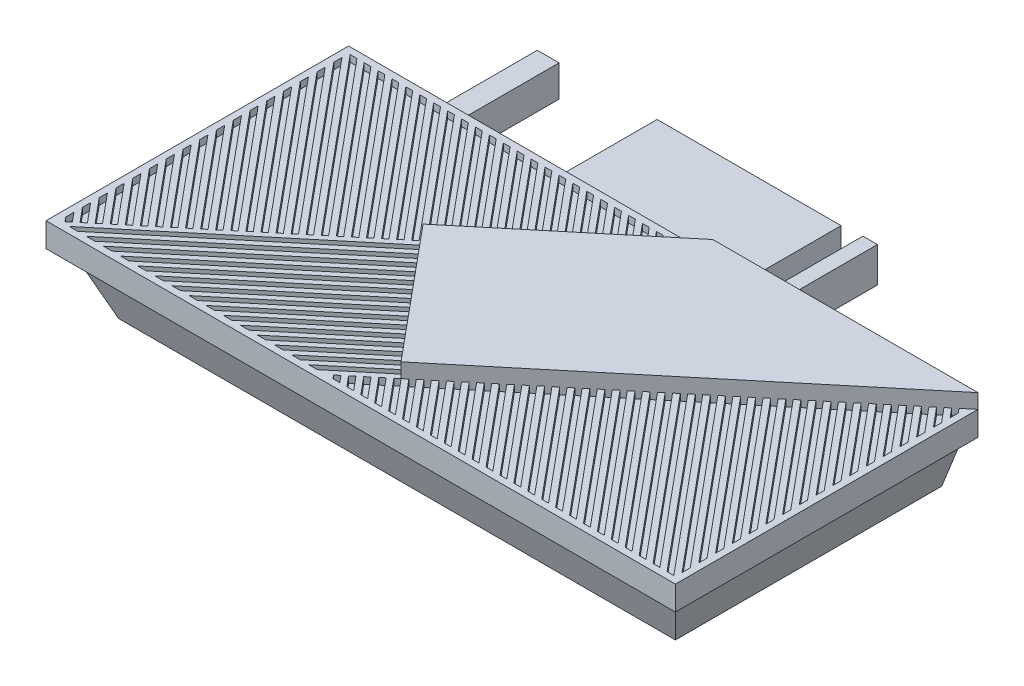
SolidWorks part; units mm, degrees
ref_plane "Front Plane" through (0, 0, 0) normal (0, 0, 1) x (1, 0, 0)
ref_plane "Top Plane" through (0, 0, 0) normal (0, 1, 0) x (1, 0, 0)
ref_plane "Right Plane" through (0, 0, 0) normal (1, 0, 0) x (0, 0, -1)
sketch "Sketch1" plane through (0, 0, 0) normal (0, 1, 0) x (1, 0, 0)
  line L1 (-130, 62.5) -> (130, 62.5)
  line L2 (-130, 62.5) -> (-130, -62.5)
  line L3 (-130, -62.5) -> (130, -62.5)
  line L4 (130, 62.5) -> (130, -62.5)
  line L5 (-130, 62.5) -> (130, -62.5) construction
  line L6 (-130, -62.5) -> (130, 62.5) construction
  point P0 (0, 0)
  dimension "D1" = 260
  dimension "D2" = 125
extrude "Boss-Extrude1" add sketch "Sketch1" against normal blind 10
ref_plane "Plane1" through (0, -35, 0) normal (0, -1, 0) x (-1, 0, 0)
sketch "Sketch2" plane through (0, -35, 0) normal (0, -1, 0) x (-1, 0, 0)
  line L1 (-115, -47.5) -> (115, -47.5)
  line L2 (-115, -47.5) -> (-115, 62.5)
  line L3 (-115, 62.5) -> (115, 62.5)
  line L4 (115, -47.5) -> (115, 62.5)
  line L5 (-130, 62.5) -> (130, 62.5) construction
  point P6 (0, 62.5)
  dimension "D1" = 110
  dimension "D2" = 230
sketch "Sketch3" plane through (0, -10, 0) normal (0, -1, 0) x (1, 0, 0)
  line L0 (130, -62.5) -> (-130, -62.5) construction
  line L1 (-125, 57.5) -> (125, 57.5)
  line L2 (-125, 57.5) -> (-125, -62.5)
  line L3 (-125, -62.5) -> (125, -62.5)
  line L4 (125, 57.5) -> (125, -62.5)
  point P10 (0, 57.5)
  dimension "D1" = 250
  dimension "D2" = 120
loft "Loft1" add profiles "Sketch2", "Sketch3" connector at (115, -35, 47.5) connector at (125, -10, 57.5)
sketch "Sketch4" plane through (0, 0, 0) normal (0, 1, 0) x (1, 0, 0)
  line L0 (130, 62.5) -> (-0.1894, -45.6603)
  line L1 (-0.1894, -45.6603) -> (-44.9215, 8.1825)
  line L2 (-44.9215, 8.1825) -> (20.4589, 62.5)
  line L3 (130, 62.5) -> (-130, 62.5) construction
  line L4 (20.4589, 62.5) -> (130, 62.5)
  line L6 (-44.9215, 8.1825) -> (-130, -62.5) construction
  dimension "D1" = 70
  dimension "D3" = 85
extrude "Boss-Extrude2" add sketch "Sketch4" along normal blind 6
shell "Shell2" thickness 2.75 removed face at (-3.5217, 0, -3.5746)
sketch "Sketch7" plane through (0, 0, 0) normal (0, 1, 0) x (1, 0, 0)
  line L0 (-0.1894, -45.6603) -> (-44.9215, 8.1825)
  line L2 (-44.9215, 8.1825) -> (20.4589, 62.5)
  line L3 (20.4589, 62.5) -> (130, 62.5)
  line L4 (130, 62.5) -> (-0.1894, -45.6603)
extrude "Boss-Extrude5" add sketch "Sketch7" against normal blind 2.75
sketch "Sketch6" plane through (0, 0, 0) normal (0, 1, 0) x (1, 0, 0)
  line L0 (-44.9215, 8.1825) -> (-130, -62.5)
  line L1 (-130, -62.5) -> (-126.4664, -62.5)
  line L2 (-130, -62.5) -> (130, -62.5) construction
  line L3 (-126.4664, -62.5) -> (-43.4786, 6.4456)
  line L4 (-44.9215, 8.1825) -> (-0.1894, -45.6603) construction
  line L5 (-43.4786, 6.4456) -> (-44.9215, 8.1825)
  line L6 (-123.5805, -65.9737) -> (-40.5926, 2.9719)
  line L7 (-42.0356, 4.7087) -> (-127.1141, -65.9737)
  line L8 (-127.1141, -65.9737) -> (-123.5805, -65.9737)
  line L9 (-40.5926, 2.9719) -> (-42.0356, 4.7087)
  line L10 (-120.6945, -69.4475) -> (-37.7067, -0.5018)
  line L11 (-39.1496, 1.235) -> (-124.2281, -69.4475)
  line L12 (-124.2281, -69.4475) -> (-120.6945, -69.4475)
  line L13 (-37.7067, -0.5018) -> (-39.1496, 1.235)
  line L14 (-117.8086, -72.9212) -> (-34.8207, -3.9756)
  line L15 (-36.2637, -2.2387) -> (-121.3422, -72.9212)
  line L16 (-121.3422, -72.9212) -> (-117.8086, -72.9212)
  line L17 (-34.8207, -3.9756) -> (-36.2637, -2.2387)
  line L18 (-114.9227, -76.3949) -> (-31.9348, -7.4493)
  line L19 (-33.3778, -5.7124) -> (-118.4562, -76.3949)
  line L20 (-118.4562, -76.3949) -> (-114.9227, -76.3949)
  line L21 (-31.9348, -7.4493) -> (-33.3778, -5.7124)
  line L22 (-112.0367, -79.8686) -> (-29.0489, -10.923)
  line L23 (-30.4918, -9.1862) -> (-115.5703, -79.8686)
  line L24 (-115.5703, -79.8686) -> (-112.0367, -79.8686)
  line L25 (-29.0489, -10.923) -> (-30.4918, -9.1862)
  line L26 (-109.1508, -83.3424) -> (-26.1629, -14.3967)
  line L27 (-27.6059, -12.6599) -> (-112.6844, -83.3424)
  line L28 (-112.6844, -83.3424) -> (-109.1508, -83.3424)
  line L29 (-26.1629, -14.3967) -> (-27.6059, -12.6599)
  line L30 (-106.2648, -86.8161) -> (-23.277, -17.8705)
  line L31 (-24.7199, -16.1336) -> (-109.7984, -86.8161)
  line L32 (-109.7984, -86.8161) -> (-106.2648, -86.8161)
  line L33 (-23.277, -17.8705) -> (-24.7199, -16.1336)
  line L34 (-103.3789, -90.2898) -> (-20.391, -21.3442)
  line L35 (-21.834, -19.6073) -> (-106.9125, -90.2898)
  line L36 (-106.9125, -90.2898) -> (-103.3789, -90.2898)
  line L37 (-20.391, -21.3442) -> (-21.834, -19.6073)
  line L38 (-100.4929, -93.7635) -> (-17.5051, -24.8179)
  line L39 (-18.9481, -23.0811) -> (-104.0265, -93.7635)
  line L40 (-104.0265, -93.7635) -> (-100.4929, -93.7635)
  line L41 (-17.5051, -24.8179) -> (-18.9481, -23.0811)
  line L42 (-97.607, -97.2373) -> (-14.6191, -28.2916)
  line L43 (-16.0621, -26.5548) -> (-101.1406, -97.2373)
  line L44 (-101.1406, -97.2373) -> (-97.607, -97.2373)
  line L45 (-14.6191, -28.2916) -> (-16.0621, -26.5548)
  line L46 (-94.7211, -100.711) -> (-11.7332, -31.7654)
  line L47 (-13.1762, -30.0285) -> (-98.2546, -100.711)
  line L48 (-98.2546, -100.711) -> (-94.7211, -100.711)
  line L49 (-11.7332, -31.7654) -> (-13.1762, -30.0285)
  line L50 (-91.8351, -104.1847) -> (-8.8473, -35.2391)
  line L51 (-10.2902, -33.5022) -> (-95.3687, -104.1847)
  line L52 (-95.3687, -104.1847) -> (-91.8351, -104.1847)
  line L53 (-8.8473, -35.2391) -> (-10.2902, -33.5022)
  line L54 (-88.9492, -107.6584) -> (-5.9613, -38.7128)
  line L55 (-7.4043, -36.976) -> (-92.4828, -107.6584)
  line L56 (-92.4828, -107.6584) -> (-88.9492, -107.6584)
  line L57 (-5.9613, -38.7128) -> (-7.4043, -36.976)
  line L58 (-86.0632, -111.1322) -> (-3.0754, -42.1865)
  line L59 (-4.5184, -40.4497) -> (-89.5968, -111.1322)
  line L60 (-89.5968, -111.1322) -> (-86.0632, -111.1322)
  line L61 (-3.0754, -42.1865) -> (-4.5184, -40.4497)
  line L62 (-83.1773, -114.6059) -> (-0.1894, -45.6603)
  line L63 (-1.6324, -43.9234) -> (-86.7109, -114.6059)
  line L64 (-86.7109, -114.6059) -> (-83.1773, -114.6059)
  line L65 (-0.1894, -45.6603) -> (-1.6324, -43.9234)
  dimension "D1" = 2.2581
  dimension "D3" = 70
  dimension "D2" = 16
extrude "Boss-Extrude6" add sketch "Sketch6" against normal blind 2.75
sketch "Sketch8" plane through (0, -10, 0) normal (0, -1, 0) x (1, 0, 0)
  line L1 (-130, 62.5) -> (15.5362, 62.5)
  line L2 (-130, 62.5) -> (-130, 143.892)
  line L3 (-130, 143.892) -> (15.5362, 143.892)
  line L4 (15.5362, 62.5) -> (15.5362, 143.892)
extrude "Cut-Extrude1" cut sketch "Sketch8" against normal through all both and the other way through all
sketch "Sketch9" plane through (0, 0, -62.5) normal (0, 0, -1) x (-1, 0, 0)
  line L0 (130, -10) -> (130, 0) construction
  line L1 (-20.4589, 0) -> (130, 0) construction
  circle A0 centre (111.5, -14.125) radius 6.625
  circle A1 centre (60, -14.125) radius 6.625
  dimension "D3" = 13.25
  dimension "D1" = 18.5
  dimension "D2" = 14.125
  dimension "D4" = 70
extrude "Boss-Extrude7" add sketch "Sketch9" along normal blind 3.3
sketch "Sketch10" plane through (0, 0, -65.8) normal (0, 0, -1) x (-1, 0, 0)
  circle A0 centre (60, -14.125) radius 5
  circle A1 centre (111.5, -14.125) radius 5
  dimension "D1" = 10
extrude "Cut-Extrude4" cut sketch "Sketch10" against normal blind 1
mirror "Mirror1" about plane through (0, 0, 0) normal (1, 0, 0) of "Cut-Extrude4", "Boss-Extrude7"
sketch "Sketch11" plane through (0, 0, 0) normal (0, 1, 0) x (1, 0, 0)
  line L0 (17.1488, 59.75) -> (15.412, 58.307)
  line L1 (20.4589, 62.5) -> (-44.9215, 8.1825) construction
  line L2 (15.412, 58.307) -> (-80.4425, 173.6843)
  line L3 (-80.4425, 173.6843) -> (-78.7056, 175.1273)
  line L4 (-78.7056, 175.1273) -> (17.1488, 59.75)
  line L5 (12.0103, 55.481) -> (-83.8441, 170.8583)
  line L6 (-82.1073, 172.3012) -> (13.7472, 56.9239)
  line L7 (13.7472, 56.9239) -> (12.0103, 55.481)
  line L8 (-83.8441, 170.8583) -> (-82.1073, 172.3012)
  line L9 (8.6087, 52.6549) -> (-87.2458, 168.0322)
  line L10 (-85.5089, 169.4752) -> (10.3455, 54.0979)
  line L11 (10.3455, 54.0979) -> (8.6087, 52.6549)
  line L12 (-87.2458, 168.0322) -> (-85.5089, 169.4752)
  line L13 (5.207, 49.8288) -> (-90.6474, 165.2061)
  line L14 (-88.9106, 166.6491) -> (6.9439, 51.2718)
  line L15 (6.9439, 51.2718) -> (5.207, 49.8288)
  line L16 (-90.6474, 165.2061) -> (-88.9106, 166.6491)
  line L17 (1.8054, 47.0028) -> (-94.0491, 162.3801)
  line L18 (-92.3122, 163.823) -> (3.5422, 48.4457)
  line L19 (3.5422, 48.4457) -> (1.8054, 47.0028)
  line L20 (-94.0491, 162.3801) -> (-92.3122, 163.823)
  line L21 (-1.5963, 44.1767) -> (-97.4507, 159.554)
  line L22 (-95.7139, 160.997) -> (0.1406, 45.6197)
  line L23 (0.1406, 45.6197) -> (-1.5963, 44.1767)
  line L24 (-97.4507, 159.554) -> (-95.7139, 160.997)
  line L25 (-4.9979, 41.3507) -> (-100.8524, 156.728)
  line L26 (-99.1155, 158.1709) -> (-3.2611, 42.7936)
  line L27 (-3.2611, 42.7936) -> (-4.9979, 41.3507)
  line L28 (-100.8524, 156.728) -> (-99.1155, 158.1709)
  line L29 (-8.3996, 38.5246) -> (-104.254, 153.9019)
  line L30 (-102.5172, 155.3449) -> (-6.6627, 39.9676)
  line L31 (-6.6627, 39.9676) -> (-8.3996, 38.5246)
  line L32 (-104.254, 153.9019) -> (-102.5172, 155.3449)
  line L33 (-11.8012, 35.6985) -> (-107.6557, 151.0758)
  line L34 (-105.9188, 152.5188) -> (-10.0644, 37.1415)
  line L35 (-10.0644, 37.1415) -> (-11.8012, 35.6985)
  line L36 (-107.6557, 151.0758) -> (-105.9188, 152.5188)
  line L37 (-15.2029, 32.8725) -> (-111.0573, 148.2498)
  line L38 (-109.3205, 149.6927) -> (-13.466, 34.3154)
  line L39 (-13.466, 34.3154) -> (-15.2029, 32.8725)
  line L40 (-111.0573, 148.2498) -> (-109.3205, 149.6927)
  line L41 (-18.6045, 30.0464) -> (-114.459, 145.4237)
  line L42 (-112.7221, 146.8667) -> (-16.8677, 31.4894)
  line L43 (-16.8677, 31.4894) -> (-18.6045, 30.0464)
  line L44 (-114.459, 145.4237) -> (-112.7221, 146.8667)
  line L45 (-22.0062, 27.2203) -> (-117.8606, 142.5976)
  line L46 (-116.1238, 144.0406) -> (-20.2693, 28.6633)
  line L47 (-20.2693, 28.6633) -> (-22.0062, 27.2203)
  line L48 (-117.8606, 142.5976) -> (-116.1238, 144.0406)
  line L49 (-25.4078, 24.3943) -> (-121.2623, 139.7716)
  line L50 (-119.5254, 141.2145) -> (-23.671, 25.8372)
  line L51 (-23.671, 25.8372) -> (-25.4078, 24.3943)
  line L52 (-121.2623, 139.7716) -> (-119.5254, 141.2145)
  line L53 (-28.8095, 21.5682) -> (-124.664, 136.9455)
  line L54 (-122.9271, 138.3885) -> (-27.0726, 23.0112)
  line L55 (-27.0726, 23.0112) -> (-28.8095, 21.5682)
  line L56 (-124.664, 136.9455) -> (-122.9271, 138.3885)
  line L57 (-32.2111, 18.7422) -> (-128.0656, 134.1194)
  line L58 (-126.3287, 135.5624) -> (-30.4743, 20.1851)
  line L59 (-30.4743, 20.1851) -> (-32.2111, 18.7422)
  line L60 (-128.0656, 134.1194) -> (-126.3287, 135.5624)
  line L61 (-35.6128, 15.9161) -> (-131.4673, 131.2934)
  line L62 (-129.7304, 132.7364) -> (-33.8759, 17.3591)
  line L63 (-33.8759, 17.3591) -> (-35.6128, 15.9161)
  line L64 (-131.4673, 131.2934) -> (-129.7304, 132.7364)
  line L65 (-39.0144, 13.09) -> (-134.8689, 128.4673)
  line L66 (-133.132, 129.9103) -> (-37.2776, 14.533)
  line L67 (-37.2776, 14.533) -> (-39.0144, 13.09)
  line L68 (-134.8689, 128.4673) -> (-133.132, 129.9103)
  line L69 (-42.4161, 10.264) -> (-138.2706, 125.6413)
  line L70 (-136.5337, 127.0842) -> (-40.6792, 11.7069)
  line L71 (-40.6792, 11.7069) -> (-42.4161, 10.264)
  line L72 (-138.2706, 125.6413) -> (-136.5337, 127.0842)
  line L73 (-45.8177, 7.4379) -> (-141.6722, 122.8152)
  line L74 (-139.9353, 124.2582) -> (-44.0809, 8.8809)
  line L75 (-44.0809, 8.8809) -> (-45.8177, 7.4379)
  line L76 (-141.6722, 122.8152) -> (-139.9353, 124.2582)
  line L77 (-49.2194, 4.6118) -> (-145.0739, 119.9891)
  line L78 (-143.337, 121.4321) -> (-47.4825, 6.0548)
  line L79 (-47.4825, 6.0548) -> (-49.2194, 4.6118)
  line L80 (-145.0739, 119.9891) -> (-143.337, 121.4321)
  line L81 (-52.621, 1.7858) -> (-148.4755, 117.1631)
  line L82 (-146.7386, 118.606) -> (-50.8842, 3.2287)
  line L83 (-50.8842, 3.2287) -> (-52.621, 1.7858)
  line L84 (-148.4755, 117.1631) -> (-146.7386, 118.606)
  line L85 (-56.0227, -1.0403) -> (-151.8772, 114.337)
  line L86 (-150.1403, 115.78) -> (-54.2858, 0.4027)
  line L87 (-54.2858, 0.4027) -> (-56.0227, -1.0403)
  line L88 (-151.8772, 114.337) -> (-150.1403, 115.78)
  line L89 (-59.4243, -3.8663) -> (-155.2788, 111.5109)
  line L90 (-153.542, 112.9539) -> (-57.6875, -2.4234)
  line L91 (-57.6875, -2.4234) -> (-59.4243, -3.8663)
  line L92 (-155.2788, 111.5109) -> (-153.542, 112.9539)
  line L93 (-62.826, -6.6924) -> (-158.6805, 108.6849)
  line L94 (-156.9436, 110.1279) -> (-61.0891, -5.2494)
  line L95 (-61.0891, -5.2494) -> (-62.826, -6.6924)
  line L96 (-158.6805, 108.6849) -> (-156.9436, 110.1279)
  line L97 (-66.2276, -9.5185) -> (-162.0821, 105.8588)
  line L98 (-160.3453, 107.3018) -> (-64.4908, -8.0755)
  line L99 (-64.4908, -8.0755) -> (-66.2276, -9.5185)
  line L100 (-162.0821, 105.8588) -> (-160.3453, 107.3018)
  line L101 (-69.6293, -12.3445) -> (-165.4838, 103.0328)
  line L102 (-163.7469, 104.4757) -> (-67.8924, -10.9016)
  line L103 (-67.8924, -10.9016) -> (-69.6293, -12.3445)
  line L104 (-165.4838, 103.0328) -> (-163.7469, 104.4757)
  line L105 (-73.0309, -15.1706) -> (-168.8854, 100.2067)
  line L106 (-167.1486, 101.6497) -> (-71.2941, -13.7276)
  line L107 (-71.2941, -13.7276) -> (-73.0309, -15.1706)
  line L108 (-168.8854, 100.2067) -> (-167.1486, 101.6497)
  line L109 (-76.4326, -17.9967) -> (-172.2871, 97.3806)
  line L110 (-170.5502, 98.8236) -> (-74.6957, -16.5537)
  line L111 (-74.6957, -16.5537) -> (-76.4326, -17.9967)
  line L112 (-172.2871, 97.3806) -> (-170.5502, 98.8236)
  line L113 (-79.8343, -20.8227) -> (-175.6887, 94.5546)
  line L114 (-173.9519, 95.9975) -> (-78.0974, -19.3798)
  line L115 (-78.0974, -19.3798) -> (-79.8343, -20.8227)
  line L116 (-175.6887, 94.5546) -> (-173.9519, 95.9975)
  line L117 (-83.2359, -23.6488) -> (-179.0904, 91.7285)
  line L118 (-177.3535, 93.1715) -> (-81.499, -22.2058)
  line L119 (-81.499, -22.2058) -> (-83.2359, -23.6488)
  line L120 (-179.0904, 91.7285) -> (-177.3535, 93.1715)
  line L121 (-86.6376, -26.4749) -> (-182.492, 88.9024)
  line L122 (-180.7552, 90.3454) -> (-84.9007, -25.0319)
  line L123 (-84.9007, -25.0319) -> (-86.6376, -26.4749)
  line L124 (-182.492, 88.9024) -> (-180.7552, 90.3454)
  line L125 (-90.0392, -29.3009) -> (-185.8937, 86.0764)
  line L126 (-184.1568, 87.5194) -> (-88.3023, -27.8579)
  line L127 (-88.3023, -27.8579) -> (-90.0392, -29.3009)
  line L128 (-185.8937, 86.0764) -> (-184.1568, 87.5194)
  line L129 (-93.4409, -32.127) -> (-189.2953, 83.2503)
  line L130 (-187.5585, 84.6933) -> (-91.704, -30.684)
  line L131 (-91.704, -30.684) -> (-93.4409, -32.127)
  line L132 (-189.2953, 83.2503) -> (-187.5585, 84.6933)
  line L133 (-96.8425, -34.953) -> (-192.697, 80.4243)
  line L134 (-190.9601, 81.8672) -> (-95.1056, -33.5101)
  line L135 (-95.1056, -33.5101) -> (-96.8425, -34.953)
  line L136 (-192.697, 80.4243) -> (-190.9601, 81.8672)
  line L137 (-100.2442, -37.7791) -> (-196.0986, 77.5982)
  line L138 (-194.3618, 79.0412) -> (-98.5073, -36.3361)
  line L139 (-98.5073, -36.3361) -> (-100.2442, -37.7791)
  line L140 (-196.0986, 77.5982) -> (-194.3618, 79.0412)
  line L141 (-103.6458, -40.6052) -> (-199.5003, 74.7721)
  line L142 (-197.7634, 76.2151) -> (-101.9089, -39.1622)
  line L143 (-101.9089, -39.1622) -> (-103.6458, -40.6052)
  line L144 (-199.5003, 74.7721) -> (-197.7634, 76.2151)
  line L145 (-107.0475, -43.4312) -> (-202.9019, 71.9461)
  line L146 (-201.1651, 73.389) -> (-105.3106, -41.9883)
  line L147 (-105.3106, -41.9883) -> (-107.0475, -43.4312)
  line L148 (-202.9019, 71.9461) -> (-201.1651, 73.389)
  line L149 (-110.4491, -46.2573) -> (-206.3036, 69.12)
  line L150 (-204.5667, 70.563) -> (-108.7122, -44.8143)
  line L151 (-108.7122, -44.8143) -> (-110.4491, -46.2573)
  line L152 (-206.3036, 69.12) -> (-204.5667, 70.563)
  line L153 (-113.8508, -49.0834) -> (-209.7052, 66.2939)
  line L154 (-207.9684, 67.7369) -> (-112.1139, -47.6404)
  line L155 (-112.1139, -47.6404) -> (-113.8508, -49.0834)
  line L156 (-209.7052, 66.2939) -> (-207.9684, 67.7369)
  line L157 (-117.2524, -51.9094) -> (-213.1069, 63.4679)
  line L158 (-211.37, 64.9109) -> (-115.5156, -50.4664)
  line L159 (-115.5156, -50.4664) -> (-117.2524, -51.9094)
  line L160 (-213.1069, 63.4679) -> (-211.37, 64.9109)
  line L161 (-120.6541, -54.7355) -> (-216.5085, 60.6418)
  line L162 (-214.7717, 62.0848) -> (-118.9172, -53.2925)
  line L163 (-118.9172, -53.2925) -> (-120.6541, -54.7355)
  line L164 (-216.5085, 60.6418) -> (-214.7717, 62.0848)
  line L165 (-124.0557, -57.5615) -> (-219.9102, 57.8158)
  line L166 (-218.1733, 59.2587) -> (-122.3189, -56.1186)
  line L167 (-122.3189, -56.1186) -> (-124.0557, -57.5615)
  line L168 (-219.9102, 57.8158) -> (-218.1733, 59.2587)
  line L169 (-127.4574, -60.3876) -> (-223.3118, 54.9897)
  line L170 (-221.575, 56.4327) -> (-125.7205, -58.9446)
  line L171 (-125.7205, -58.9446) -> (-127.4574, -60.3876)
  line L172 (-223.3118, 54.9897) -> (-221.575, 56.4327)
  dimension "D1" = 2.2581
  dimension "D2" = 150
  dimension "D4" = 188
  dimension "D3" = 43
extrude "Boss-Extrude8" add sketch "Sketch11" against normal blind 2.75
sketch "Sketch12" plane through (0, 0, 0) normal (0, 1, 0) x (1, 0, 0)
  line L0 (-130, -62.5) -> (-255, -62.5)
  line L1 (-255, -62.5) -> (-255, 197.5)
  line L2 (-255, 197.5) -> (35, 197.5)
  line L3 (35, 197.5) -> (35, 62.5)
  line L4 (130, 62.5) -> (20.4589, 62.5) construction
  line L5 (35, 62.5) -> (-130, 62.5)
  line L6 (-130, 62.5) -> (-130, -62.5)
  dimension "D1" = 125
  dimension "D2" = 260
  dimension "D3" = 290
extrude "Cut-Extrude5" cut sketch "Sketch12" against normal blind 3
ref_axis "Axis1" through (0, -37.0501, 0) along (0, 1, 0)
pattern_circular "CirPattern1" count 2 over 360 about axis through (0, -37.0501, 0) along (0, 1, 0) of "Boss-Extrude8", "Cut-Extrude5"
sketch "Sketch14" plane through (0, 0, -62.5) normal (0, 0, -1) x (-1, 0, 0)
  line L0 (-20.4589, 0) -> (130, 0) construction
  line L1 (-29, -7) -> (47, -7)
  line L2 (-29, -7) -> (-29, -20)
  line L3 (-29, -20) -> (47, -20)
  line L4 (47, -7) -> (47, -20)
  line L5 (-44, -6.25) -> (-38, -6.25)
  line L6 (-44, -6.25) -> (-44, -20.75)
  line L7 (-44, -20.75) -> (-38, -20.75)
  line L8 (-38, -6.25) -> (-38, -20.75)
  line L9 (87.5, -7) -> (96.5, -7)
  line L10 (87.5, -7) -> (87.5, -20)
  line L11 (87.5, -20) -> (96.5, -20)
  line L12 (96.5, -7) -> (96.5, -20)
  line L14 (130, -10) -> (130, 0) construction
  point P12 (-29, -13.5)
  point P13 (-38, -13.5)
  point P14 (87.5, -13.5)
  dimension "D1" = 20
  dimension "D2" = 7
  dimension "D3" = 159
  dimension "D4" = 83
  dimension "D5" = 42.5
  dimension "D6" = 33.5
  dimension "D7" = 20
  dimension "D8" = 168
  dimension "D9" = 20.75
  dimension "D10" = 174
extrude "Boss-Extrude9" add sketch "Sketch14" along normal blind 44.45
sketch "Sketch15" plane through (0, -2.75, 0) normal (0, -1, 0) x (1, 0, 0)
  line L1 (127.25, -59.75) -> (-127.25, -59.75)
  line L2 (127.25, -59.75) -> (127.25, 59.75)
  line L3 (127.25, 59.75) -> (-127.25, 59.75)
  line L4 (-127.25, -59.75) -> (-127.25, 59.75)
extrude "Boss-Extrude10" add sketch "Sketch15" along normal blind 1.5
sketch "Sketch17" plane through (0, -35, 0) normal (0, -1, 0) x (1, 0, 0)
  line L0 (98.5, -62.5) -> (98.5, 47.5) construction
  line L1 (-115, -62.5) -> (115, -62.5) construction
  line L2 (115, 47.5) -> (-115, 47.5) construction
  line L3 (115, -62.5) -> (115, 47.5) construction
  line L4 (98.5, 0.5) -> (98.5, -15.5) construction
  line L5 (101, 0.5) -> (101, -15.5)
  line L6 (96, 0.5) -> (96, -15.5)
  arc A0 (101, 0.5) -> (96, 0.5) centre (98.5, 0.5) ccw
  arc A1 (96, -15.5) -> (101, -15.5) centre (98.5, -15.5) ccw
  circle A2 centre (98.5, -7.5) radius 5
  point P10 (98.5, -7.5)
  point P16 (98.5, -7.5)
  dimension "D3" = 5
  dimension "D4" = 10
  dimension "D1" = 16.5
  dimension "D2" = 16
extrude "Cut-Extrude6" cut sketch "Sketch17" against normal blind 1.5 contours L6 A2 | L5 A2 L6 | A2 L5 A0 L6 | A2 L6 A1 L5 | L5 A2 region at (98.5, -35, -0.1004) region at (102.0251, -35, -7.5) region at (98.5, -35, -7.5) region at (98.5, -35, -14.8996) region at (94.9749, -35, -7.5)
mirror "Mirror2" about plane through (0, 0, 0) normal (1, 0, 0) of "Cut-Extrude6"
equation "\"D1@Sketch6\"=70/31"
